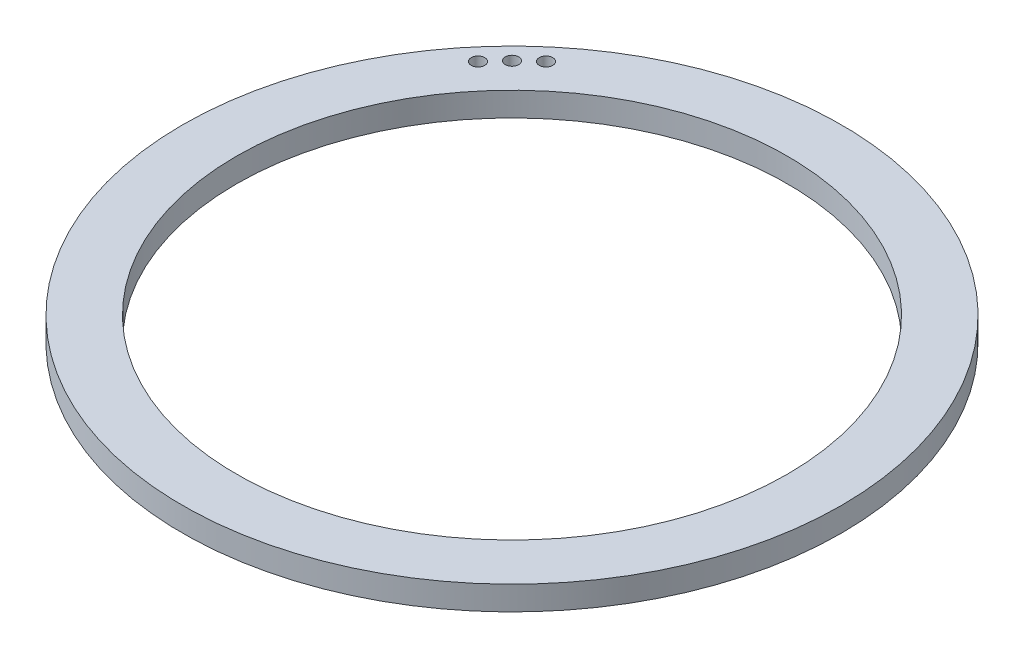
SolidWorks part; units mm, degrees
material "Oak"
ref_plane "Front Plane" through (0, 0, 0) normal (0, 0, 1) x (1, 0, 0)
ref_plane "Top Plane" through (0, 0, 0) normal (0, 1, 0) x (1, 0, 0)
ref_plane "Right Plane" through (0, 0, 0) normal (1, 0, 0) x (0, 0, -1)
sketch "Sketch1" plane through (0, 0, 0) normal (0, 0, 1) x (1, 0, 0)
  line L0 (0, -200000) -> (0, 218797.9879) construction
  line L5 (0, -200000) -> (0, 218797.9879) construction
  line L6 (174.1012, 206.3724) -> (174.1012, 193.6724)
  line L7 (145.5262, 206.3724) -> (174.1012, 206.3724)
  line L8 (174.1012, 193.6724) -> (145.5262, 193.6724)
  line L9 (145.5262, 193.6724) -> (145.5262, 206.3724)
revolve "Revolve1" add sketch "Sketch1" angle 360 about L5
hole_wizard "9/32 (0.28125) Diameter Hole1" positions "Sketch5" profile "Sketch6" hole size "9/32" standard "ANSI Inch" end condition through all
sketch "Sketch5" plane through (0, 206.3724, 0) normal (0, 1, 0) x (1, 0, 0)
  point P0 (-116.373, 116.373)
  point P3 (-107.0457, 125.0062)
  point P6 (-125.0062, 107.0457)
sketch "Sketch6" plane through (-116.373, 206.3724, -116.373) normal (1, 0, 0) x (0, 0, 1)
  line L0 (0, 0) -> (0, 12.7)
  line L1 (0, 12.7) -> (3.5719, 12.7)
  line L2 (3.5719, 12.7) -> (3.5719, 0)
  line L5 (3.5719, 0) -> (0, 0)
  line L11 (0, -6.35) -> (0, 107.95) construction
  dimension "Thru Hole Dia." = 7.1437
  dimension "Thru Hole Depth" = 12.7
